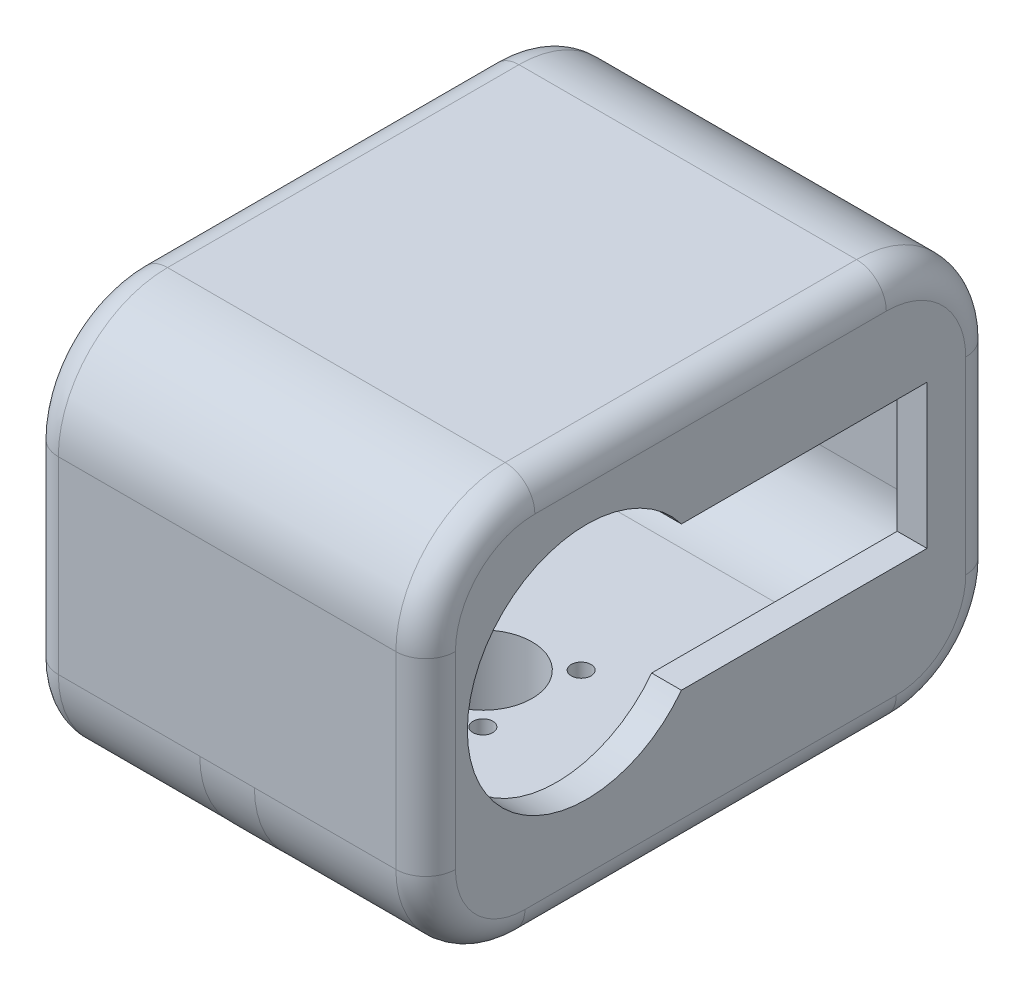
SolidWorks part; units mm, degrees
material "PLA"
ref_plane "Front Plane" through (0, 0, 0) normal (1, 0, 0) x (0, 1, 0)
ref_plane "Top Plane" through (0, 0, 0) normal (0, 0, 1) x (0, 1, 0)
ref_plane "Right Plane" through (0, 0, 0) normal (0, 1, 0) x (-1, 0, 0)
sketch "Sketch1" plane through (0, 0, 0) normal (1, 0, 0) x (0, 0, 1)
  line L0 (-35.2, 0) -> (10.2, 0) construction
  line L1 (-35.2, 12.5) -> (10.2, 12.5)
  line L2 (-35.2, 12.5) -> (-35.2, -12.5)
  line L3 (-35.2, -12.5) -> (10.2, -12.5)
  line L4 (10.2, 12.5) -> (10.2, -12.5)
  line L6 (-34.3002, 7.25) -> (-34.3002, -7.25)
  line L7 (-34.3002, -7.25) -> (-8.6676, -7.25)
  line L8 (-8.6676, 7.25) -> (-34.3002, 7.25)
  line L12 (-12.5, 12.5) -> (-12.5, 25.9141) construction
  line L13 (-12.5, -12.5) -> (-12.5, -25.9141) construction
  line L14 (-38.2, 7.5) -> (-38.2, -7.5)
  line L15 (-30.2, -15.5) -> (5.2, -15.5)
  line L16 (13.2, 7.5) -> (13.2, -7.5)
  line L17 (-30.2, 15.5) -> (5.2, 15.5)
  line L18 (-38.2, 15.5) -> (-38.2, -15.5) construction
  line L19 (-38.2, -15.5) -> (13.2, -15.5) construction
  line L20 (13.2, 15.5) -> (13.2, -15.5) construction
  line L21 (-38.2, 15.5) -> (13.2, 15.5) construction
  line L22 (-30.2, 18.5) -> (5.2, 18.5)
  line L23 (16.2, 7.5) -> (16.2, -7.5)
  line L24 (-30.2, -18.5) -> (5.2, -18.5)
  line L25 (-41.2, 7.5) -> (-41.2, -7.5)
  line L39 (-8.6676, -7.25) -> (-6.8875, -7.25)
  line L40 (-6.8875, 7.25) -> (-8.6676, 7.25)
  arc A2 (-8.6676, 7.25) -> (-8.6676, -7.25) centre (0, 0) ccw
  circle A8 centre (0, 0) radius 12
  arc A13 (-8.6676, 7.25) -> (-8.6676, -7.25) centre (0, 0) ccw
  circle A14 centre (0, 0) radius 10
  arc A15 (-38.2, -7.5) -> (-30.2, -15.5) centre (-30.2, -7.5) ccw
  arc A16 (5.2, -15.5) -> (13.2, -7.5) centre (5.2, -7.5) ccw
  arc A17 (13.2, 7.5) -> (5.2, 15.5) centre (5.2, 7.5) ccw
  arc A18 (-38.2, 7.5) -> (-30.2, 15.5) centre (-30.2, 7.5) cw
  arc A19 (-41.2, 7.5) -> (-30.2, 18.5) centre (-30.2, 7.5) cw
  arc A20 (16.2, 7.5) -> (5.2, 18.5) centre (5.2, 7.5) ccw
  arc A21 (5.2, -18.5) -> (16.2, -7.5) centre (5.2, -7.5) ccw
  arc A22 (-41.2, -7.5) -> (-30.2, -18.5) centre (-30.2, -7.5) ccw
  dimension "D1" = 20
  dimension "D5" = 1.3
  dimension "D6" = 25
  dimension "D8" = 10.2
  dimension "D10" = 8
  dimension "D2" = 25.6326
  dimension "D3" = 25.6326
  dimension "D4" = 14.5
  dimension "D7" = 45.4
  dimension "D9" = 3
  dimension "D11" = 2
  dimension "D12" = 3
extrude "Boss-Extrude1" add sketch "Sketch1" along normal blind 40 contours L1 | L2 | L3 | A8 L7 L6 L8 L4 L1 L2 L3 | L4 A8 | A8 L8 L6 L7 | A14 | A14 L39 L7 A8 L4 L8 L40 | A14 L40 A2 L39 | L4 A8 | L8 A8 L7 A2 | L25 A22 L24 A21 L23 A20 L22 A19 L14 A18 L17 A17 L16 A16 L15 A15 region at (0, -11.9817, -12.5) region at (0, 0, 10.9248) region at (0, 0, 10.1689) region at (0, 0, -22.7509) region at (0, -7.1012, -9.115) region at (0, -7.0984, -7.7776) region at (0, 0, 0) region at (0, -12.7324, -35.4324) region at (0, -17.8171, -12.5)
sketch "Sketch5" plane through (0, 0, 0) normal (0, 0, 1) x (0, 1, 0)
  line L1 (-21.5, 0) -> (0, 0)
  line L2 (-21.5, 0) -> (-21.5, -40)
  line L3 (-21.5, -40) -> (0, -40)
  line L4 (0, 0) -> (0, -40)
  line L5 (-18.5, -40) -> (-18.5, 0) construction
  line L6 (-7.5, -40) -> (7.5, -40) construction
  dimension "D1" = 3
extrude "Boss-Extrude2" add sketch "Sketch5" along normal through all and the other way through all
extrude "Cut-Extrude1" cut sketch "Sketch1<9>" against normal through all both and the other way through all contours A8 L8 L6 L7 | A14 | A14 L39 L7 A8 L4 L8 L40 | A14 L40 A2 L39 | L8 A8 L7 A2 | L4 A8 region at (0, 0, 10.9248) region at (0, 0, 10.1689) region at (0, 0, -22.7509) region at (0, -7.1012, -9.115) region at (0, -7.0984, -7.7776) region at (0, 0, 0)
sketch "Sketch1<9>" plane through (0, 0, 0) normal (1, 0, 0) x (0, 0, 1) same geometry as "Sketch1"
extrude "Cut-Extrude3" cut sketch "Sketch1<10>" along normal offset from surface 3 and the other way through all contours A18 L14 A15 L15 A16 L16 A17 L17 A8 L4 L3 L2 L1 | A8 L7 L6 L8 L4 L1 L2 L3 region at (0, -11.9817, -12.5) region at (0, -12.7324, -35.4324) up to face at (40, 2.2594, -12.5)
sketch "Sketch1<10>" plane through (0, 0, 0) normal (1, 0, 0) x (0, 0, 1) same geometry as "Sketch1"
sketch "Sketch7" plane through (0, -21.5, 0) normal (0, -1, 0) x (1, 0, 0)
  line L0 (20, 16.2) -> (20, -41.2) construction
  line L1 (0, 16.2) -> (40, 16.2) construction
  line L2 (0, -41.2) -> (40, -41.2) construction
  line L3 (15.05, -4.6123) -> (24.95, -4.6123) construction
  line L4 (40, -9.5623) -> (0, -9.5623) construction
  line L5 (0, 16.2) -> (0, -41.2) construction
  line L6 (24.95, -4.6123) -> (24.95, -14.5123) construction
  line L7 (15.05, -4.6123) -> (15.05, -14.5123) construction
  line L8 (15.05, -14.5123) -> (24.95, -14.5123) construction
  circle A1 centre (20, -9.5623) radius 10
  circle A2 centre (15.05, -4.6123) radius 1
  circle A3 centre (24.95, -4.6123) radius 1
  circle A4 centre (24.95, -14.5123) radius 1
  circle A5 centre (15.05, -14.5123) radius 1
  circle A6 centre (20, -9.5623) radius 4.95
  dimension "D1" = 20
  dimension "D2" = 2
  dimension "D3" = 9.9
extrude "Boss-Extrude3" add sketch "Sketch7" along normal blind 2 contours A1 A6 A5 A4 A3 A2 region at (10.2828, -21.5, -9.5623)
fillet "Fillet1" radius 10 1 edges at (20, -21.5, 0.4377)
extrude "Cut-Extrude4" cut sketch "Sketch7<3>" against normal up to next contours A2 | A3 | A4 | A5 | A6 region at (15.05, -21.5, -4.6123) region at (24.95, -21.5, -4.6123) region at (24.95, -21.5, -14.5123) region at (15.05, -21.5, -14.5123) region at (20, -21.5, -9.5623)
sketch "Sketch7<3>" plane through (0, -21.5, 0) normal (0, -1, 0) x (1, 0, 0) same geometry as "Sketch7"
fillet "Fillet2" radius 10 2 edges at (20, -21.5, -41.2) (20, -21.5, 16.2)
fillet "Fillet3" radius 3 24 edges at (0, 15.2782, -37.9782) (0, 18.5, -12.5) (0, 15.2782, 12.9782) (0, -2, 16.2) (0, -18.5711, 13.2711) (0, -21.5, -12.5) (0, -18.5711, -38.2711) (0, -2, -41.2) (0, 0, 13.2) (0, 13.1569, 10.8569) (0, 15.5, -12.5) (0, 13.1569, -35.8569) (0, 0, -38.2) (0, -13.1569, -35.8569) (0, -15.5, -12.5) (0, -13.1569, 10.8569) (40, -18.5711, 13.2711) (40, -2, 16.2) (40, 15.2782, 12.9782) (40, 18.5, -12.5) (40, 15.2782, -37.9782) (40, -2, -41.2) (40, -18.5711, -38.2711) (40, -21.5, -12.5)
